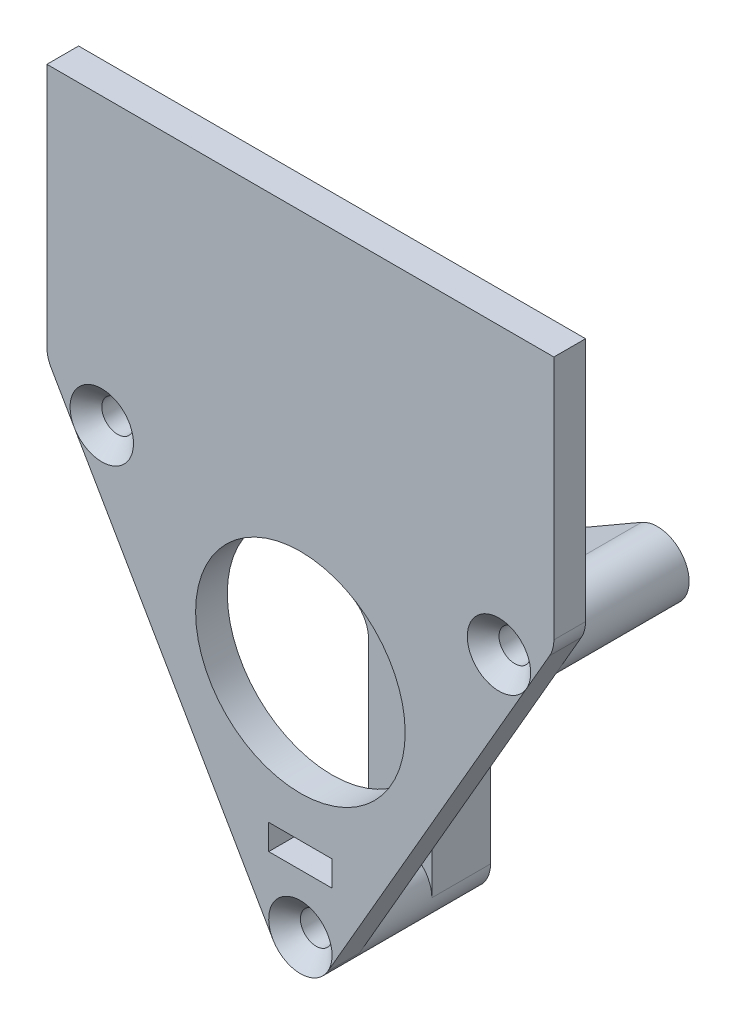
SolidWorks part; units mm, degrees
material "6061 Alloy"
ref_plane "Front" through (0, 0, 0) normal (0, 0, 1) x (1, 0, 0)
ref_plane "Top" through (0, 0, 0) normal (0, 1, 0) x (1, 0, 0)
ref_plane "Right" through (0, 0, 0) normal (1, 0, 0) x (0, 0, -1)
sketch "Sketch1" plane through (0, 0, 0) normal (0, 0, 1) x (1, 0, 0)
  line L0 (0, -58.6588) -> (-50.8, 29.3294)
  line L1 (-50.8, 29.3294) -> (-50.8, 80.1294)
  line L2 (-50.8, 80.1294) -> (50.8, 80.1294)
  line L3 (50.8, 80.1294) -> (50.8, 29.3294)
  line L4 (50.8, 29.3294) -> (0, -58.6588)
  line L5 (-50.8, 29.3294) -> (50.8, 29.3294) construction
  line L6 (-25.4, -14.6647) -> (0, 0) construction
  line L7 (0, 0) -> (0, 29.3294) construction
  line L8 (0, 0) -> (25.4, -14.6647) construction
  dimension "D1" = 101.6
  dimension "D2" = 50.8
extrude "Boss-Extrude1" add sketch "Sketch1" along normal mid plane 6.35
sketch "Sketch2" plane through (0, 0, 3.175) normal (0, 0, 1) x (1, 0, 0)
  circle A0 centre (0, 0) radius 21
  dimension "D1" = 42
extrude "Cut-Extrude1" cut sketch "Sketch2" against normal through all
fillet "Fillet1" radius 6.35 3 edges at (-50.8, 29.3294, 0) (50.8, 29.3294, 0) (0, -58.6588, 0)
sketch "Sketch3" plane through (0, 0, 3.175) normal (0, 0, 1) x (1, 0, 0)
  line L1 (-6.35, -34.29) -> (6.35, -34.29)
  line L2 (-6.35, -34.29) -> (-6.35, -29.21)
  line L3 (-6.35, -29.21) -> (6.35, -29.21)
  line L4 (6.35, -34.29) -> (6.35, -29.21)
  line L5 (-6.35, -34.29) -> (6.35, -29.21) construction
  line L6 (-6.35, -29.21) -> (6.35, -34.29) construction
  point P0 (0, -31.75)
  point P5 (0, 0)
  dimension "D1" = 31.75
  dimension "D2" = 12.7
  dimension "D3" = 5.08
extrude "Cut-Extrude2" cut sketch "Sketch3" against normal through all
sketch "Sketch5" plane through (0, 0, -3.175) normal (0, 0, -1) x (-1, 0, 0)
  circle A0 centre (0, -45.9588) radius 6.35
  arc A1 (-5.4993, -49.1338) -> (5.4993, -49.1338) centre (0, -45.9588) ccw construction
extrude "Boss-Extrude3" add sketch "Sketch5" along normal blind 25.4
sketch "Sketch6" plane through (0, 0, 3.175) normal (0, 0, 1) x (1, 0, 0)
  circle A0 centre (0, -45.9588) radius 3.175
  arc A1 (-5.4993, -49.1338) -> (5.4993, -49.1338) centre (0, -45.9588) ccw construction
  dimension "D1" = 6.35
extrude "Cut-Extrude3" cut sketch "Sketch6" against normal blind 25.4
chamfer "Chamfer2" distance 3.175 angle 45 1 edges at (3.175, -45.9588, 3.175)
sketch "Sketch8" plane through (0, 0, -28.575) normal (0, 0, -1) x (-1, 0, 0)
  line L1 (-6.35, -45.9588) -> (6.35, -45.9588)
  line L2 (-6.35, -45.9588) -> (-6.35, 0)
  line L3 (-6.35, 0) -> (6.35, 0)
  line L4 (6.35, -45.9588) -> (6.35, 0)
  line L5 (-6.35, -45.9588) -> (6.35, 0) construction
  line L6 (-6.35, 0) -> (6.35, -45.9588) construction
  circle A0 centre (0, -45.9588) radius 6.35 construction
  point P0 (0, -22.9794)
  point P5 (0, 0)
  point P8 (0, 0)
  circle M5 centre (0, -45.9588) radius 6.35
extrude "Boss-Extrude4" add sketch "Sketch8" against normal offset from surface (11.75 mm away) 20 contours L4 L3 L2 M5 region at (0, -20.5103, -28.575) up to face at (0, -31.75, 3.175)
pattern_circular "CirPattern2" count 3 over 360 about axis through (0, 0, -3.175) along (0, 0, 1) of "Boss-Extrude3", "Cut-Extrude3", "Chamfer2", "Boss-Extrude4"
fillet "Fillet2" radius 6.35 3 edges at (6.35, -3.6662, -22.7) (0, 7.3323, -22.7) (-6.35, -3.6662, -22.7)
sketch "Sketch9" plane through (0, 0, -28.575) normal (0, 0, -1) x (-1, 0, 0)
  circle A0 centre (0, 0) radius 3
  dimension "D1" = 6
extrude "Cut-Extrude4" cut sketch "Sketch9" against normal through all
